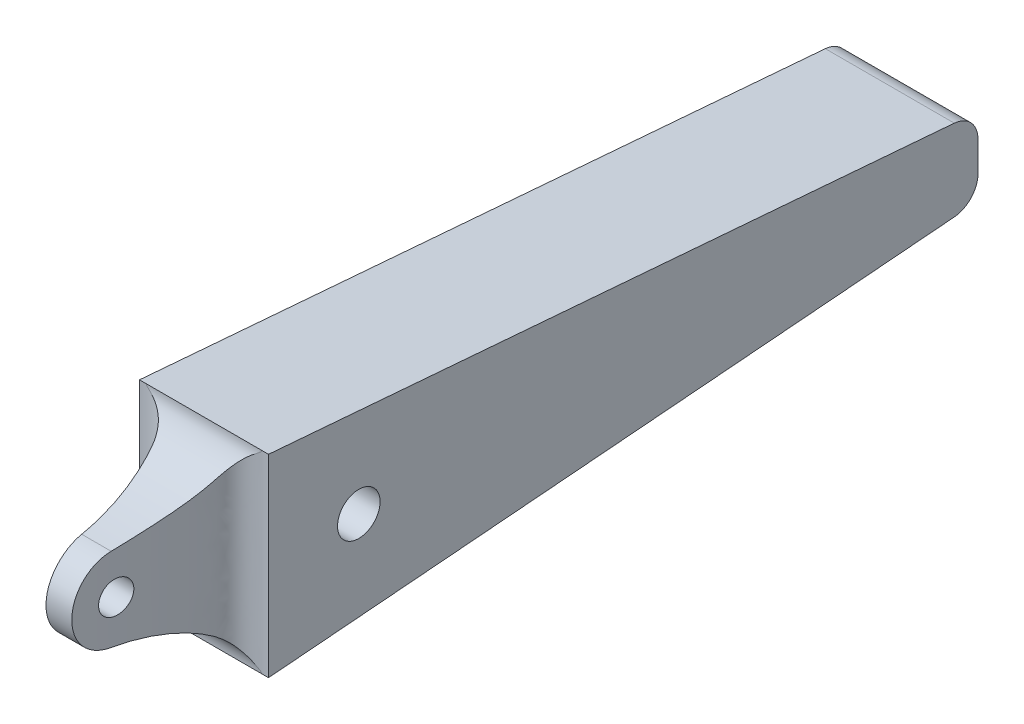
SolidWorks part; units mm, degrees
ref_plane "Front Plane" through (0, 0, 0) normal (1, 0, 0) x (0, 1, 0)
ref_plane "Top Plane" through (0, 0, 0) normal (0, 0, 1) x (0, 1, 0)
ref_plane "Right Plane" through (0, 0, 0) normal (0, 1, 0) x (-1, 0, 0)
sketch "Sketch1" plane through (0, 0, 0) normal (1, 0, 0) x (0, 1, 0)
  line L0 (0, -28.3905) -> (0, 48) construction
  line L1 (3, 0) -> (-3, 0)
  line L2 (-3, 0) -> (-7.5, 55)
  line L3 (3, 0) -> (7.5, 55)
  line L4 (0, 66.25) -> (0, 51.4514) construction
  circle A1 centre (0, 63) radius 1.25
  circle A2 centre (0, 48) radius 1.65
  arc A3 (3.2322, 63.3399) -> (-3.2322, 63.3399) centre (0, 63) ccw
  ellipse E0 centre (-7.5, 66.25) end of major axis (-7.5, 77.5) minor radius 4.4182 (-7.5, 55) -> (-3.2322, 63.3399) ccw
  ellipse E1 centre (7.5, 66.25) end of major axis (7.5, 77.5) minor radius 4.4182 (7.5, 55) -> (3.2322, 63.3399) cw
  point P9 (0, 0)
  dimension "D4" = 2.5
  dimension "D5" = 3.3
  dimension "D7" = 7
  dimension "D8" = 2
  dimension "D1" = 15
  dimension "D2" = 6
  dimension "D3" = 55
  dimension "D6" = 15
extrude "Boss-Extrude1" add sketch "Sketch1" along normal blind 10
fillet "Fillet3" radius 2 2 edges at (5, 3, 0) (5, -3, 0)
sketch "Sketch4" plane through (0, 0, 0) normal (0, 1, 0) x (-1, 0, 0)
  line L0 (-5, 55) -> (-5, 70.3533) construction
  line L1 (-10, 55) -> (0, 55) construction
  line L2 (0, 66.25) -> (-10, 66.25) construction
  line L3 (-10, 55) -> (-10, 66.25)
  line L4 (-10, 66.25) -> (-10, 63.3399) construction
  line L5 (-10, 66.25) -> (-6, 66.25)
  line L6 (-4, 66.25) -> (0, 66.25)
  line L7 (0, 66.25) -> (0, 55)
  spline S0 degree 3 poles (-6, 66.25) (-6.0649, 62.3548) (-6.7765, 58.4387) (-7.8921, 54.898) (-10, 55) knots 0 0 0 0 0.696387 1 1 1 1
  spline S1 degree 3 poles (-4, 66.25) (-3.9351, 62.3548) (-3.2235, 58.4387) (-2.1079, 54.898) (0, 55) knots 0 0 0 0 0.696387 1 1 1 1
  point P6 (0, 55)
  dimension "D1" = 1
extrude "Cut-Extrude1" cut sketch "Sketch4" against normal through all and the other way through all contours L6 S1 L7 | S0 L3 L5 region at (1.7271, 0, 61.2157)
